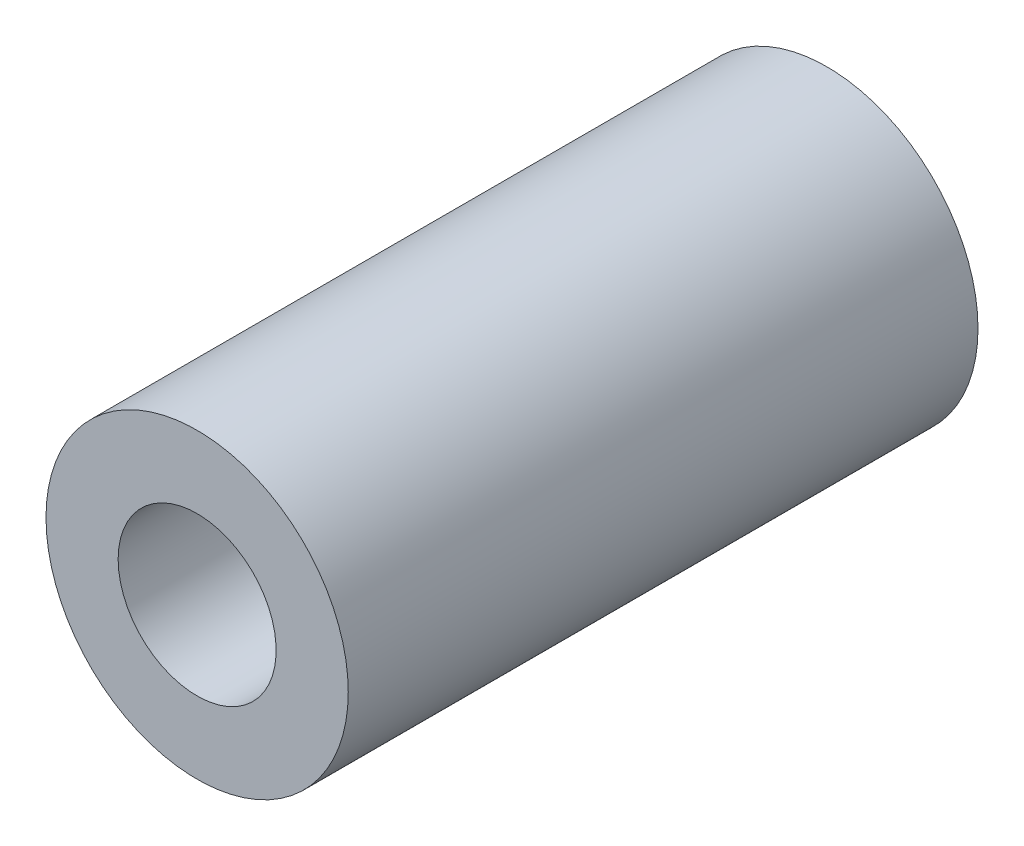
SolidWorks part; units mm, degrees
ref_plane "Front Plane" through (0, 0, 0) normal (0, 0, 1) x (1, 0, 0)
ref_plane "Top Plane" through (0, 0, 0) normal (0, 1, 0) x (1, 0, 0)
ref_plane "Right Plane" through (0, 0, 0) normal (1, 0, 0) x (0, 0, -1)
sketch "Sketch1" plane through (0, 0, 0) normal (0, 0, 1) x (1, 0, 0)
  circle A0 centre (0, 0) radius 4.7625
  circle A1 centre (0, 0) radius 2.4892
  dimension "D1" = 9.525
  dimension "D2" = 4.9784
extrude "Boss-Extrude1" add sketch "Sketch1" along normal mid plane 19.8438
